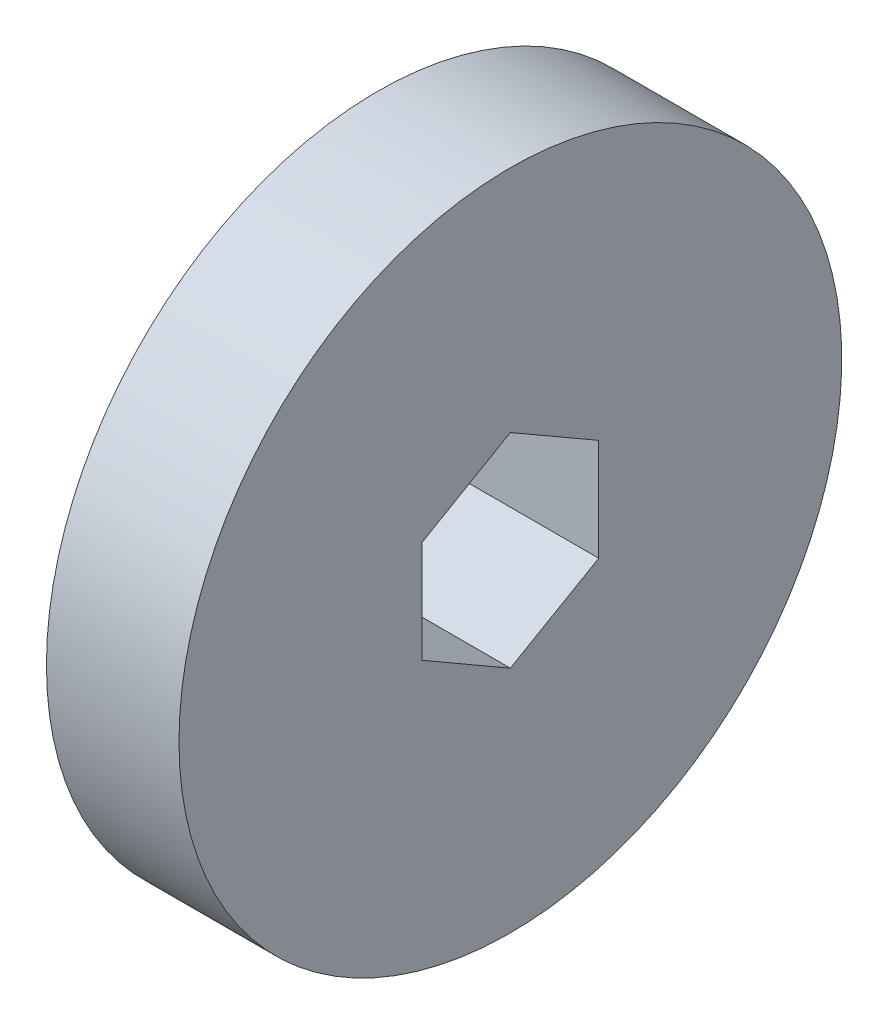
SolidWorks part; units mm, degrees
ref_plane "Front Plane" through (0, 0, 0) normal (0, 0, 1) x (1, 0, 0)
ref_plane "Top Plane" through (0, 0, 0) normal (0, 1, 0) x (1, 0, 0)
ref_plane "Right Plane" through (0, 0, 0) normal (1, 0, 0) x (0, 0, -1)
sketch "Sketch2" plane through (0, 0, 0) normal (1, 0, 0) x (0, 0, -1)
  line L1 (0, 7.3323) -> (-6.35, 3.6662)
  line L2 (-6.35, 3.6662) -> (-6.35, -3.6662)
  line L3 (-6.35, -3.6662) -> (0, -7.3323)
  line L4 (0, -7.3323) -> (6.35, -3.6662)
  line L5 (6.35, -3.6662) -> (6.35, 3.6662)
  line L6 (6.35, 3.6662) -> (0, 7.3323)
  circle A0 centre (0, 0) radius 23.8125
  circle A1 centre (0, 0) radius 6.35 construction
  dimension "D1" = 47.625
  dimension "D2" = 12.7
extrude "Boss-Extrude1" add sketch "Sketch2" along normal mid plane 9.525
